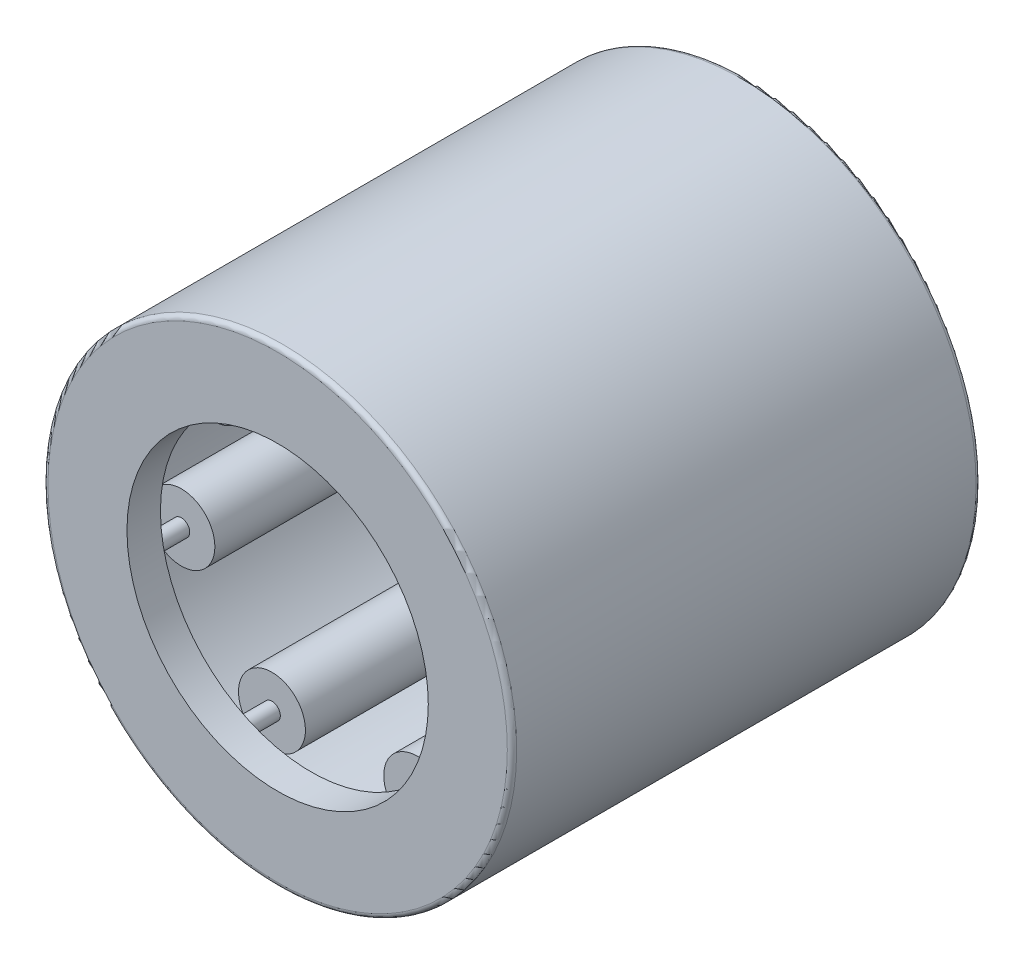
SolidWorks part; units mm, degrees
material "Alloy Steel"
ref_plane "Front Plane" through (0, 0, 0) normal (0, 0, 1) x (1, 0, 0)
ref_plane "Top Plane" through (0, 0, 0) normal (0, 1, 0) x (1, 0, 0)
ref_plane "Right Plane" through (0, 0, 0) normal (1, 0, 0) x (0, 0, -1)
sketch "Sketch1" plane through (0, 0, 0) normal (1, 0, 0) x (0, 0, -1)
  line L0 (-5.5562, 0) -> (5.5562, 0) construction
  line L1 (0, 0) -> (0, 5.5563) construction
  line L2 (-5.5562, 0) -> (-5.5562, 5.5563) construction
  line L3 (-5.5562, 5.5563) -> (5.5562, 5.5563)
  line L4 (5.5562, 5.5563) -> (5.5562, 0) construction
  line L5 (5.5562, 0) -> (4.7625, 0) construction
  line L6 (4.7625, 0) -> (4.7625, 4.7625) construction
  line L7 (4.7625, 4.7625) -> (-4.7625, 4.7625)
  line L8 (-4.7625, 4.7625) -> (-4.7625, 0) construction
  line L9 (-4.7625, 0) -> (-5.5562, 0) construction
  line L10 (-5.5562, 5.5563) -> (-5.5562, 3.5719)
  line L11 (-5.5562, 3.5719) -> (-4.7625, 3.5719)
  line L12 (-4.7625, 3.5719) -> (-4.7625, 4.7625)
  line L13 (4.7625, 5.5563) -> (4.7625, 4.7625) construction
  line L14 (4.7625, 4.7625) -> (4.7625, 3.5719)
  line L15 (4.7625, 3.5719) -> (5.5562, 3.5719)
  line L16 (5.5562, 3.5719) -> (5.5562, 5.5563)
  line L17 (4.7625, 4.7625) -> (4.7625, 3.9688) construction
  line L18 (4.7625, 3.9688) -> (4.7625, 3.175) construction
  point P5 (0, 3.175)
  dimension "Width" = 11.1125
  dimension "OD" = 11.1125
  dimension "Shaft Dia" = 6.35
revolve "Revolve1" add sketch "Sketch1" angle 360 about L0
sketch "Sketch2" plane through (0, 0, 0) normal (1, 0, 0) x (0, 0, -1)
  line L0 (4.7625, 4.7625) -> (-4.7625, 4.7625) construction
  line L1 (-3.9688, 3.9688) -> (3.9688, 3.9688) construction
  line L2 (-3.9688, 3.9688) -> (-3.9688, 4.7625) construction
  line L3 (-3.9688, 4.7625) -> (3.9688, 4.7625)
  line L4 (3.9688, 3.9688) -> (3.9688, 4.7625) construction
  line L5 (4.7625, 3.5719) -> (5.5562, 3.5719) construction
  line L6 (-4.7625, 3.9687) -> (-3.9688, 3.9688) construction
  line L7 (3.9688, 3.9688) -> (4.7625, 3.9687) construction
  line L8 (-5.5562, 3.5719) -> (-4.7625, 3.5719) construction
  line L9 (-3.9688, 4.1672) -> (-3.9688, 3.7703) construction
  line L10 (-4.7625, 3.9687) -> (-4.7625, 3.5719) construction
  line L11 (-3.9688, 4.7625) -> (-3.9688, 4.1672)
  line L12 (3.9688, 4.7625) -> (3.9688, 4.1672)
  line L13 (3.9688, 4.1672) -> (-3.9688, 4.1672)
  line L14 (0, 4.7625) -> (0, 3.175) construction
  line L15 (-4.7625, 3.5719) -> (-4.7625, 4.7625) construction
  line L16 (-3.9688, 3.7703) -> (-4.7625, 3.7703) construction
  line L17 (0, 0) -> (5.5562, 0) construction
  line L31 (5.5562, -5.5563) -> (5.5562, 5.5563) construction
  point P16 (0, 3.9688)
revolve "Revolve2" add sketch "Sketch2" angle 360 about L1
sketch "Sketch3" plane through (0, 0, 0) normal (1, 0, 0) x (0, 0, -1)
  line L0 (4.7625, 4.7625) -> (4.7625, 3.5719) construction
  line L1 (-4.7625, 3.9687) -> (4.7625, 3.9687)
  line L2 (-4.7625, 3.9687) -> (-4.7625, 4.1672)
  line L3 (-4.7625, 4.1672) -> (4.7625, 4.1672)
  line L4 (4.7625, 3.9687) -> (4.7625, 4.1672)
  line L5 (0, 0) -> (5.5562, 0) construction
  line L6 (5.5562, -5.5563) -> (5.5562, 5.5563) construction
revolve "Revolve3" add sketch "Sketch3" angle 360 about L1
ref_axis "Axis1" through (0, 0, -5.5562) along (0, 0, 1)
pattern_circular "CirPattern1" count 7 every 51.429 about axis through (0, 0, -5.5562) along (0, 0, 1) of bodies 166 167
fillet "Fillet1" radius 0.1111 2 edges at (5.5563, 0, -5.5562) (5.5563, 0, 5.5562)
sketch "Sketch4" plane through (0, 0, 0) normal (1, 0, 0) x (0, 0, -1)
  line L1 (5.4451, 3.175) -> (3.9688, 3.175)
  line L2 (5.4451, 3.175) -> (5.4451, 3.5719)
  line L3 (5.4451, 3.5719) -> (3.9688, 3.5719)
  line L4 (3.9688, 3.175) -> (3.9688, 3.5719)
  line L5 (-5.5562, 3.5719) -> (-4.7625, 3.5719) construction
  line L6 (5.4451, -5.5563) -> (5.4451, 5.5563) construction
  line L7 (3.9688, 4.7625) -> (3.9688, 4.1672) construction
revolve "Revolve4" [suppressed] add sketch "Sketch4" angle 360 about L0
sketch "Sketch5" plane through (0, 0, 0) normal (1, 0, 0) x (0, 0, -1)
  line L0 (-5.4451, 5.5563) -> (-5.4451, -5.5563) construction
  line L1 (-3.9688, 3.175) -> (-5.4451, 3.175)
  line L2 (-3.9688, 3.175) -> (-3.9688, 3.5719)
  line L3 (-3.9688, 3.5719) -> (-5.4451, 3.5719)
  line L4 (-5.4451, 3.175) -> (-5.4451, 3.5719)
  line L6 (-3.9688, 4.7625) -> (-3.9688, 4.1672) construction
  line L7 (-5.5562, 3.5719) -> (-4.7625, 3.5719) construction
revolve "Revolve5" [suppressed] add sketch "Sketch5" angle 360 about L0
sketch "Front View" plane through (0, 0, 0) normal (0, 0, 1) x (1, 0, 0)
  circle A0 centre (0, 0) radius 3.175 construction
  circle A1 centre (0, 0) radius 5.5562 construction
  dimension "OD" = 11.1125
  dimension "ID" = 6.35
sketch "Right View" plane through (0, 0, 0) normal (1, 0, 0) x (0, 0, -1)
  line L0 (-5.5562, 5.5563) -> (5.5562, 5.5563) construction
  dimension "Width" = 11.1125
ref_axis "Center Axis 1" through (0, 0, -5.4451) along (0, 0, 1)
ref_plane "Contact Plane 1" through (0, 0, 5.5562) normal (0, 0, 1) x (1, 0, 0)
ref_plane "Contact Plane 2" through (0, 0, -5.5562) normal (0, 0, -1) x (-1, 0, 0)
equation "\"Rollers@CirPattern1\" = \"OD@Sketch1\"*16"
equation "\"D1@Fillet1\" = \"OD@Sketch1\"*.01"
equation "\"Angle@CirPattern1\"= 360 / \"Rollers@CirPattern1\""
equation "\"OD@Front View\"=\"OD@Sketch1\""
equation "\"ID@Front View\"=\"Shaft Dia@Sketch1\""
equation "\"Width@Right View\"=\"Width@Sketch1\""
